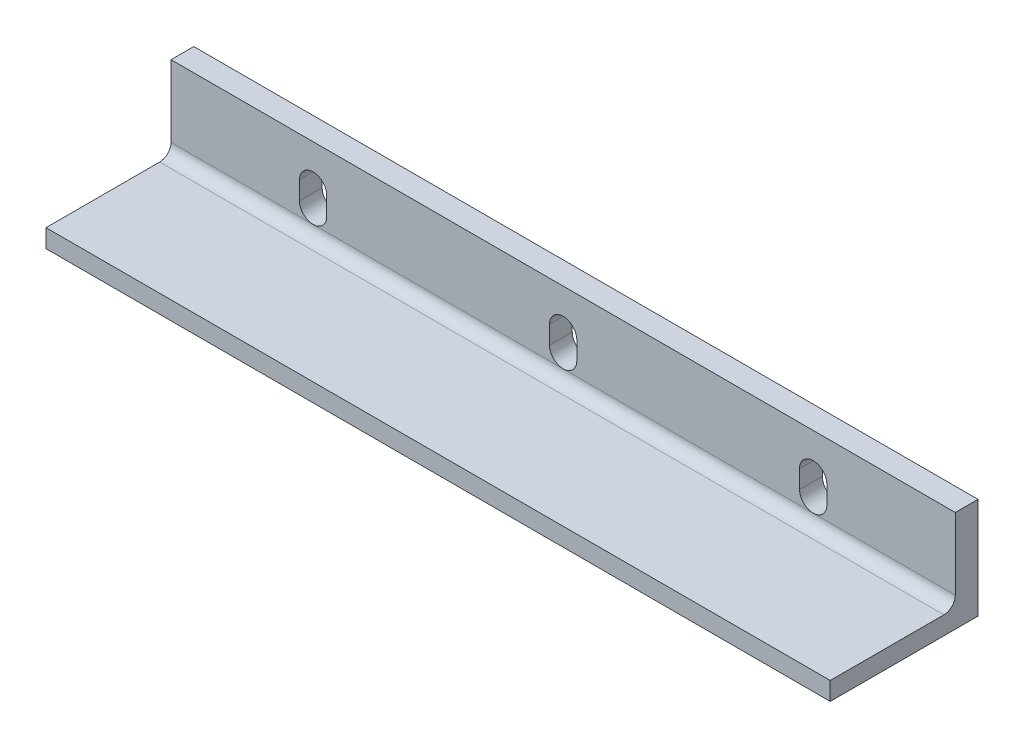
SolidWorks part; units mm, degrees
material "FR4_stuffedProtoboard"
ref_plane "Front Plane" through (0, 0, 0) normal (0, 0, 1) x (1, 0, 0)
ref_plane "Top Plane" through (0, 0, 0) normal (0, 1, 0) x (1, 0, 0)
ref_plane "Right Plane" through (0, 0, 0) normal (1, 0, 0) x (0, 0, -1)
sketch "Sketch1" plane through (0, 0, 0) normal (0, 1, 0) x (1, 0, 0)
  line L1 (-34.5, -6.5) -> (34.5, -6.5)
  line L2 (-34.5, -6.5) -> (-34.5, 6.5)
  line L3 (-34.5, 6.5) -> (34.5, 6.5)
  line L4 (34.5, -6.5) -> (34.5, 6.5)
  line L5 (-34.5, -6.5) -> (34.5, 6.5) construction
  line L6 (-34.5, 6.5) -> (34.5, -6.5) construction
  point P0 (0, 0)
  dimension "D1" = 13
  dimension "D2" = 69
extrude "Boss-Extrude1" add sketch "Sketch1" along normal blind 1.6
sketch "Sketch2" plane through (0, 1.6, 0) normal (0, 1, 0) x (1, 0, 0)
  line L0 (34.5, -6.5) -> (34.5, 6.5) construction
  line L1 (-34.5, 6.5) -> (34.5, 6.5)
  line L2 (-34.5, 6.5) -> (-34.5, 4.5)
  line L3 (-34.5, 4.5) -> (34.5, 4.5)
  line L4 (34.5, 6.5) -> (34.5, 4.5)
  dimension "D1" = 2
extrude "Boss-Extrude2" add sketch "Sketch2" along normal blind 7.3
fillet "Fillet1" radius 1 1 edges at (0, 1.6, -4.5)
sketch "Sketch3" plane through (0, 0, -6.5) normal (0, 0, 1) x (1, 0, 0)
  line L0 (0, 0) -> (0, 4.6) construction
  line L1 (22, 4.6) -> (-22, 4.6) construction
  point P6 (0, 4.6)
  dimension "D1" = 4.6
  dimension "D2" = 44
hole_wizard "M2 Clearance Slot1" positions "Sketch7" profile "Sketch8" size "M2" standard "ANSI Metric" slot yes end condition through all
sketch "Sketch7" plane through (0, 0, -4.5) normal (0, 0, 1) x (1, 0, 0)
  line L0 (-22, 2.6) -> (-22, 6.6) construction
  point P14 (-22, 4.6)
  point P19 (0, 4.6)
  point P22 (22, 4.6)
  dimension "D1" = 4
sketch "Sketch8" plane through (-22, 4.6, -4.5) normal (1, 0, 0) x (0, -1, 0)
  line L0 (0, 0) -> (0, 2)
  line L1 (0, 2) -> (1.2, 2)
  line L2 (1.2, 2) -> (1.2, 0)
  line L5 (1.2, 0) -> (0, 0)
  line L11 (0, -6.35) -> (0, 107.95) construction
  dimension "Thru Hole Dia." = 2.4
  dimension "Thru Hole Depth" = 2
